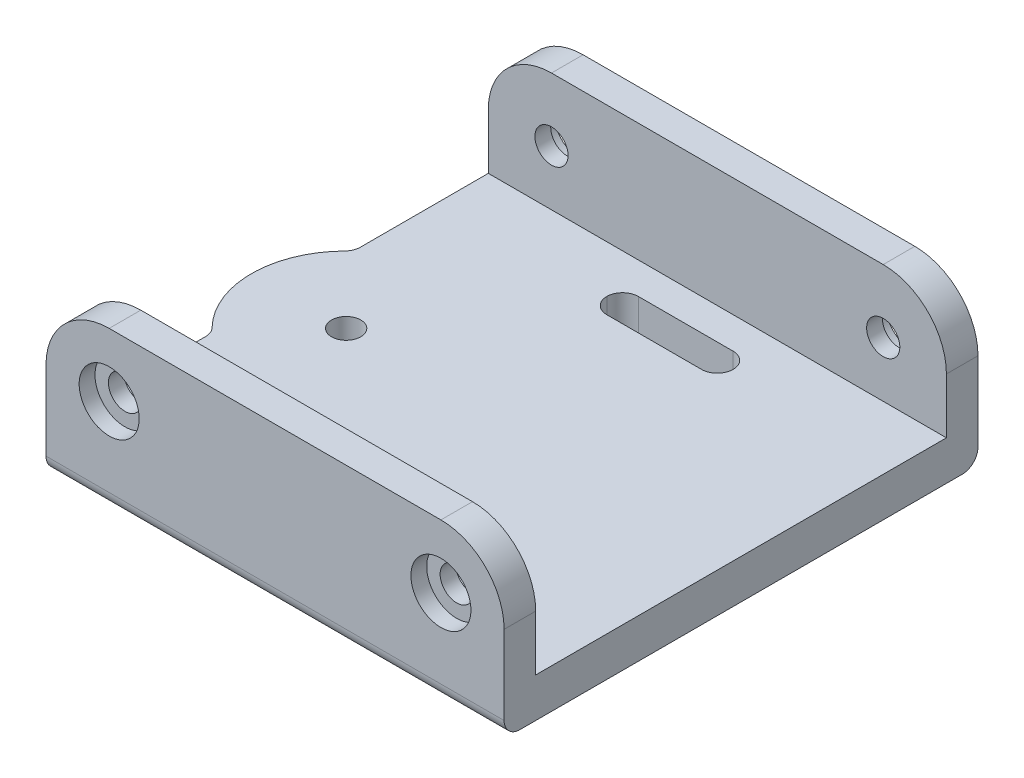
SolidWorks part; units mm, degrees
material "ABS"
ref_plane "正面" through (0, 0, 0) normal (0, 0, 1) x (1, 0, 0)
ref_plane "平面" through (0, 0, 0) normal (0, 1, 0) x (1, 0, 0)
ref_plane "右側面" through (0, 0, 0) normal (1, 0, 0) x (0, 0, -1)
sketch "ｽｹｯﾁ1" plane through (0, 0, 0) normal (1, 0, 0) x (0, 0, -1)
  line L0 (-15, -5) -> (15, -5)
  line L1 (-13, -2.5) -> (13, -2.5)
  line L8 (13, -2.5) -> (13, 5)
  line L9 (13, 5) -> (15, 5)
  line L10 (15, -5) -> (15, 5)
  line L14 (-13, -2.5) -> (-13, 5)
  line L15 (-13, 5) -> (-15, 5)
  line L16 (-15, -5) -> (-15, 5)
  point P0 (0, 0)
  point P1 (15, 0)
  point P3 (0, -5)
  point P9 (13.6789, 3.6775)
  point P13 (-12.5044, 3.6905)
  dimension "D1" = 30
  dimension "D2" = 10
  dimension "D3" = 2
  dimension "D4" = 2.5
  dimension "D5" = 0
  dimension "D6" = 0
extrude "ﾎﾞｽ - 押し出し1" add sketch "ｽｹｯﾁ1" along normal mid plane 29
hole_wizard "M2 丸平ねじ用座ぐり穴1" positions "ｽｹｯﾁ3" profile "ｽｹｯﾁ4" counterbore size "M2" standard "JIS" end condition up to next
sketch "ｽｹｯﾁ3" plane through (0, 0, -15) normal (0, 0, -1) x (-1, 0, 0)
  line L0 (-10.5, 1) -> (10.5, 1) construction
  line L2 (-14.5, 5) -> (14.5, 5) construction
  point P0 (-10.5, 1)
  point P2 (10.5, 1)
  point P10 (0, 1)
  dimension "D1" = 4
  dimension "D2" = 21
  dimension "D3" = 0
sketch "ｽｹｯﾁ4" plane through (10.5, 1, -15) normal (1, 0, 0) x (0, 1, 0)
  line L0 (0, 0) -> (0, 30)
  line L1 (0, 30) -> (1.05, 30)
  line L3 (1.05, 30) -> (1.05, 1)
  line L4 (1.05, 1) -> (1.9, 1)
  line L5 (1.9, 1) -> (1.9, 0)
  line L7 (1.9, 0) -> (0, 0)
  line L11 (0, -6.35) -> (0, 107.95) construction
  dimension "通し穴の直径" = 2.1
  dimension "通し穴の深さ" = 30
  dimension "座ぐり穴の直径" = 3.8
  dimension "座ぐり穴の深さ" = 1
sketch "ｽｹｯﾁ5" plane through (0, -5, 0) normal (0, -1, 0) x (1, 0, 0)
  circle A0 centre (-10.5, 0) radius 6
  dimension "D1" = 12
  dimension "D2" = 10.5
  dimension "D3" = 0
extrude "ﾎﾞｽ - 押し出し2" add sketch "ｽｹｯﾁ5" against normal up to surface (2.5 mm away) up to face at (0, -2.5, 0)
sketch "ｽｹｯﾁ6" plane through (0, -5, 0) normal (0, -1, 0) x (1, 0, 0)
  circle A0 centre (-10.5, 0) radius 3.5
  dimension "D1" = 7
extrude "ﾎﾞｽ - 押し出し3" add sketch "ｽｹｯﾁ6" along normal blind 2
chamfer "面取り1" distance 0.5 angle 45 1 edges at (-10.5, -7, -3.5)
sketch "ｽｹｯﾁ7" plane through (0, -7, 0) normal (0, -1, 0) x (1, 0, 0)
  circle A0 centre (-10.5, 0) radius 0.925
  dimension "D1" = 1.85
extrude "ｶｯﾄ - 押し出し1" cut sketch "ｽｹｯﾁ7" against normal up to next
fillet "ﾌｨﾚｯﾄ1" radius 4 4 edges at (-14.5, 5, 14) (14.5, 5, 14) (14.5, 5, -14) (-14.5, 5, -14)
fillet "ﾌｨﾚｯﾄ2" radius 1 4 edges at (-14.5, -3.75, -4.4721) (-14.5, -3.75, 4.4721) (0, -5, -15) (0, -5, 15)
sketch "ｽｹｯﾁ8" plane through (0, -5, 0) normal (0, -1, 0) x (1, 0, 0)
  line L0 (14.5, -15) -> (-14.5, -15) construction
  line L1 (-4, -9) -> (4, -9)
  line L2 (-4, -9) -> (-4, -11)
  line L3 (-4, -11) -> (4, -11)
  line L4 (4, -9) -> (4, -11)
  line L5 (-4, -9) -> (4, -11) construction
  line L6 (-4, -11) -> (4, -9) construction
  point P4 (0, -10)
  dimension "D1" = 2
  dimension "D2" = 4
  dimension "D3" = 0
  dimension "D4" = 8
extrude "ｶｯﾄ - 押し出し2" cut sketch "ｽｹｯﾁ8" against normal up to next
fillet "ﾌｨﾚｯﾄ3" radius 1 4 edges at (4, -3.75, -9) (-4, -3.75, -9) (-4, -3.75, -11) (4, -3.75, -11)
mirror "ﾐﾗｰ1" about plane through (0, 0, 0) normal (0, 0, 1) of "M2 丸平ねじ用座ぐり穴1"
